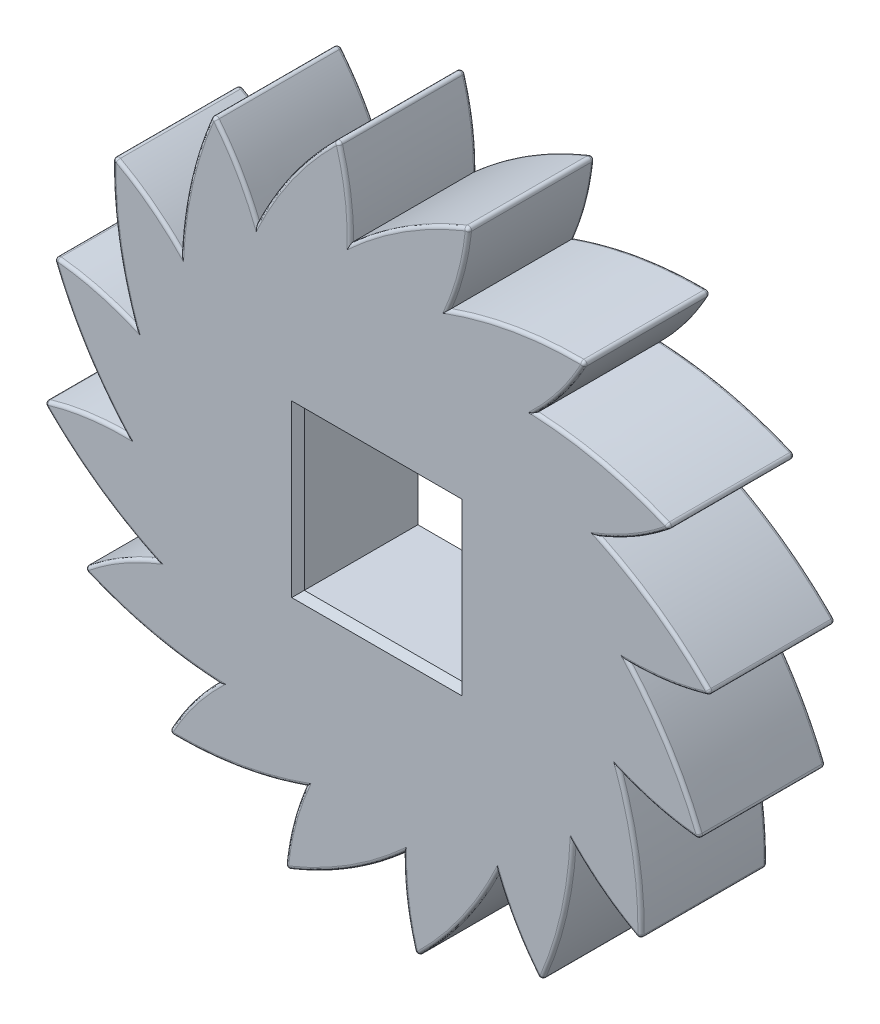
SolidWorks part; units mm, degrees
ref_plane "Front Plane" through (0, 0, 0) normal (0, 0, 1) x (1, 0, 0)
ref_plane "Top Plane" through (0, 0, 0) normal (0, 1, 0) x (1, 0, 0)
ref_plane "Right Plane" through (0, 0, 0) normal (1, 0, 0) x (0, 0, -1)
sketch "Sketch1" plane through (0, 0, 0) normal (0, 0, 1) x (1, 0, 0)
  line L0 (0, 6.8628) -> (0, -9.3943) construction
  line L1 (1.5875, 1.5875) -> (-1.5875, 1.5875)
  line L2 (-1.5875, 1.5875) -> (-1.5875, -1.5875)
  line L3 (-1.5875, -1.5875) -> (1.5875, -1.5875)
  line L4 (1.5875, 1.5875) -> (1.5875, -1.5875)
  circle A0 centre (0, 0) radius 7.366
  point P10 (0, -1.5875)
  point P11 (0, 1.5875)
  dimension "D1" = 14.732
  dimension "D2" = 1.5875
  dimension "D3" = 3.175
  dimension "D4" = 1.5875
extrude "Boss-Extrude1" add sketch "Sketch1" along normal blind 2.54
sketch "Sketch2" plane through (0, 0, 2.54) normal (0, 0, 1) x (1, 0, 0)
  circle A0 centre (0, 0) radius 5.08 construction
  circle A2 centre (0, 0) radius 7.366 construction
  arc A7 (2.7837, 6.8197) -> (-0.9985, 7.298) centre (0, 0) ccw
  spline S0 degree 2 poles (-0.5329, 5.052) (-0.5261, 6.229) (-0.9985, 7.298) knots 0 0 0 1 1 1
  spline S1 degree 2 poles (-0.5329, 5.052) (0.9138, 6.3446) (2.7837, 6.8197) knots 0 0 0 1 1 1
  point P6 (1.1298, 6.0674)
  point P12 (1.0643, 6.143)
  point P13 (2.7837, 6.8197)
  point P14 (1.1829, 6.2248)
  point P15 (-0.9985, 7.298)
  dimension "D1" = 10.16
extrude "Cut-Extrude1" cut sketch "Sketch2" against normal through all
pattern_circular "CirPattern1" count 16 over 360 about axis through (0, 0, 2.54) along (0, 0, 1) of "Cut-Extrude1"
chamfer "Chamfer1" distance 0.127 angle 45 8 edges at (0, -1.5875, 2.54) (1.5875, 0, 2.54) (0, 1.5875, 2.54) (-1.5875, 0, 2.54) (0, 1.5875, 0) (1.5875, 0, 0) (-1.5875, 0, 0) (0, -1.5875, 0)
fillet "Fillet2" radius 0.0635 80 edges at (-5.9212, -3.3023, 1.27) (-4.2067, -5.3169, 1.27) (-1.8518, -6.522, 1.27) (0.785, -6.7342, 1.27) (3.3023, -5.9212, 1.27) (5.3169, -4.2067, 1.27) (6.522, -1.8518, 1.27) (6.7342, 0.785, 1.27) (5.9212, 3.3023, 1.27) (4.2067, 5.3169, 1.27) (1.8518, 6.522, 1.27) (-0.785, 6.7342, 1.27) (-3.3023, 5.9212, 1.27) (-6.7342, -0.785, 1.27) (-5.3169, 4.2067, 1.27) (-6.522, 1.8518, 1.27)
sketch "Sketch3" plane through (0, 0, 2.54) normal (0, 0, 1) x (1, 0, 0)
  circle A0 centre (0, 0) radius 3.4496 construction
  dimension "D1" = 6.8992
